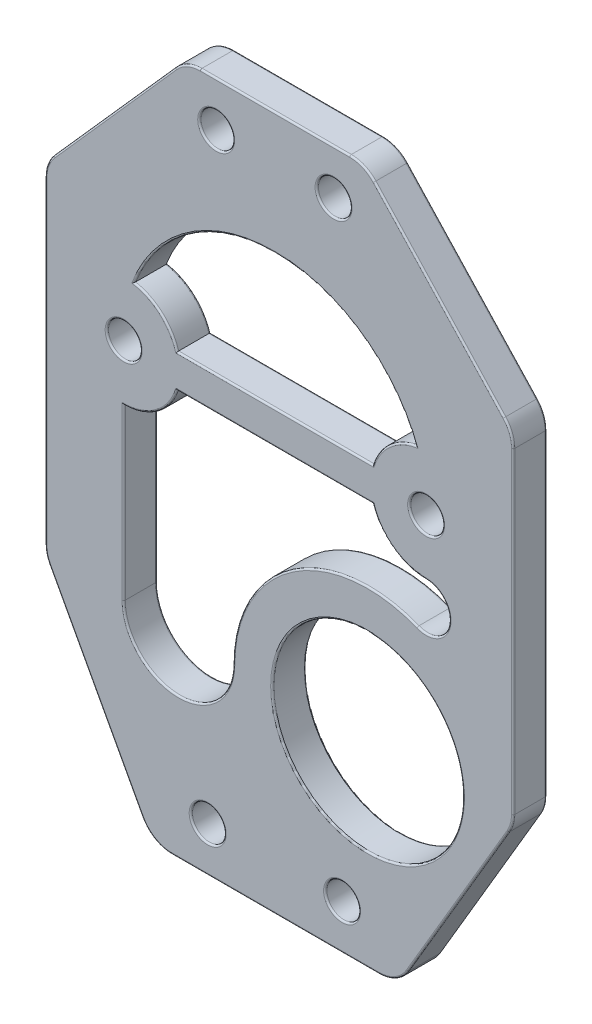
SolidWorks part; units mm, degrees
ref_plane "Front Plane" through (0, 0, 0) normal (0, 0, 1) x (1, 0, 0)
ref_plane "Top Plane" through (0, 0, 0) normal (0, 1, 0) x (1, 0, 0)
ref_plane "Right Plane" through (0, 0, 0) normal (1, 0, 0) x (0, 0, -1)
sketch "Sketch1" plane through (0, 0, 0) normal (0, 0, 1) x (1, 0, 0)
  line L0 (0, 0) -> (0, 62) construction
  line L1 (11, 0) -> (-11, 0)
  line L2 (-11, 0) -> (-20.5, 17.5997)
  line L3 (-20.5, 17.5997) -> (-20.5, 47.8997)
  line L4 (-20.5, 47.8997) -> (-7.9898, 62)
  line L5 (-7.9898, 62) -> (7.9898, 62)
  line L6 (11, 0) -> (21.2717, 17.4511)
  line L7 (21.2717, 17.4511) -> (21.2717, 47.7511)
  line L8 (21.2717, 47.7511) -> (7.9898, 62)
  line L9 (21.2717, 17.4511) -> (8.2717, 17.4511) construction
  line L10 (-13.5, 37.5997) -> (13.5, 37.5997) construction
  line L11 (-8.7303, 39.0997) -> (8.7303, 39.0997)
  line L12 (-8.7303, 36.0997) -> (8.7303, 36.0997) construction
  line L13 (-8.7303, 36.0997) -> (-8.7303, 39.0997) construction
  line L14 (-8.7303, 39.0997) -> (8.7303, 39.0997) construction
  line L15 (8.7303, 36.0997) -> (8.7303, 39.0997) construction
  line L16 (-8.7303, 36.0997) -> (8.7303, 39.0997) construction
  line L17 (-8.7303, 39.0997) -> (8.7303, 36.0997) construction
  line L18 (8.7303, 36.0997) -> (-8.7303, 36.0997)
  line L19 (13.5, 37.5997) -> (12.7283, 28.5928) construction
  line L20 (-13.5, 32.5997) -> (-13.5, 17.4511)
  circle A0 centre (-5.2398, 58) radius 1.5
  circle A1 centre (-13.5, 37.5997) radius 1.5
  circle A2 centre (-6, 4) radius 1.5
  circle A3 centre (6, 4) radius 1.5
  circle A4 centre (13.5, 37.5997) radius 1.5
  circle A5 centre (5.2398, 58) radius 1.5
  circle A6 centre (8.2717, 17.4511) radius 8.5
  circle A7 centre (13.5, 37.5997) radius 5 construction
  circle A8 centre (-13.5, 37.5997) radius 5 construction
  circle A9 centre (8.2717, 17.4511) radius 12 construction
  arc A10 (-12.5741, 42.5132) -> (12.5741, 42.5132) centre (0, 37.5997) cw
  arc A11 (-12.5741, 42.5132) -> (-8.7303, 39.0997) centre (-13.5, 37.5997) cw
  arc A12 (8.7303, 39.0997) -> (12.5741, 42.5132) centre (13.5, 37.5997) cw
  arc A13 (-8.7303, 36.0997) -> (-13.5, 32.5997) centre (-13.5, 37.5997) cw
  arc A14 (8.7303, 36.0997) -> (13.5, 32.5997) centre (13.5, 37.5997) ccw
  arc A15 (13.5, 32.5997) -> (12.7283, 28.5928) centre (13.5, 30.522) cw
  arc A16 (12.7283, 28.5928) -> (-3.7283, 17.4511) centre (8.2717, 17.4511) ccw
  arc A17 (-13.5, 17.4511) -> (-3.7283, 17.4511) centre (-8.6142, 17.4511) ccw
  dimension "D4" = 30.3
  dimension "D5" = 20
  dimension "D9" = 3
  dimension "D12" = 4
  dimension "D14" = 13
  dimension "D13" = 17
  dimension "D18" = 13.5
  dimension "D1" = 62
  dimension "D2" = 2.75
  dimension "D3" = 18.85
  dimension "D6" = 6
  dimension "D7" = 20.5
  dimension "D8" = 10.3
  dimension "D10" = 7
  dimension "D11" = 11
  dimension "D19" = 3
  dimension "D15" = 3.5
  dimension "D16" = 3.5
  dimension "D17" = 3.5
extrude "Boss-Extrude3" add sketch "Sketch1" along normal mid plane 3
fillet "Fillet1" radius 3 8 edges at (-11, 0, 0) (-20.5, 17.5997, 0) (-20.5, 47.8997, 0) (-7.9898, 62, 0) (7.9898, 62, 0) (21.2717, 47.7511, 0) (21.2717, 17.4511, 0) (11, 0, 0)
fillet "Fillet2" radius 0.15 68 edges at (-13.5, 25.0254, 1.5) (-8.6142, 12.5653, 1.5) (1.5441, 27.3879, 1.5) (15.5403, 30.1291, 1.5) (10.542, 33.5686, 1.5) (0, 36.0997, 1.5) (-10.542, 33.5686, 1.5) (16.7717, 17.4511, 1.5) (-4.5, 4, 1.5) (-12, 37.5997, 1.5) (-3.7398, 58, 1.5) (-20.4086, 17.6228, 1.5) (-20.5, 32.5592, 1.5) (-20.3047, 47.8256, 1.5) (-14.3146, 54.8714, 1.5) (-7.8712, 61.7361, 1.5) (0.022, 62, 1.5) (7.8816, 61.7511, 1.5) (14.6728, 54.8304, 1.5) (21.063, 47.669, 1.5) (21.2717, 32.4191, 1.5) (21.1661, 17.4799, 1.5) (16.3636, 9.1125, 1.5) (10.7738, 0.3957, 1.5) (0.0372, 0, 1.5) (-10.7472, 0.4237, 1.5) (-15.9951, 9.2539, 1.5) (0, 39.0997, 1.5) (10.1799, 41.3383, 1.5) (0, 51.0997, 1.5) (-10.1799, 41.3383, 1.5) (4.5, 4, 1.5) (12, 37.5997, 1.5) (3.7398, 58, 1.5) (10.542, 33.5686, -1.5) (15.5403, 30.1291, -1.5) (1.5441, 27.3879, -1.5) (-8.6142, 12.5653, -1.5) (-13.5, 25.0254, -1.5) (-10.542, 33.5686, -1.5) (0, 36.0997, -1.5) (3.7398, 58, -1.5) (4.5, 4, -1.5) (-4.5, 4, -1.5) (-3.7398, 58, -1.5) (10.7738, 0.3957, -1.5) (16.3636, 9.1125, -1.5) (21.1661, 17.4799, -1.5) (21.2717, 32.4191, -1.5) (21.063, 47.669, -1.5) (14.6728, 54.8304, -1.5) (7.8816, 61.7511, -1.5) (0.022, 62, -1.5) (-7.8712, 61.7361, -1.5) (-14.3146, 54.8714, -1.5) (-20.3047, 47.8256, -1.5) (-20.5, 32.5592, -1.5) (-20.4086, 17.6228, -1.5) (-15.9951, 9.2539, -1.5) (-10.7472, 0.4237, -1.5) (0.0372, 0, -1.5) (-12, 37.5997, -1.5) (16.7717, 17.4511, -1.5) (10.1799, 41.3383, -1.5) (0, 39.0997, -1.5) (-10.1799, 41.3383, -1.5) (0, 51.0997, -1.5) (12, 37.5997, -1.5)
